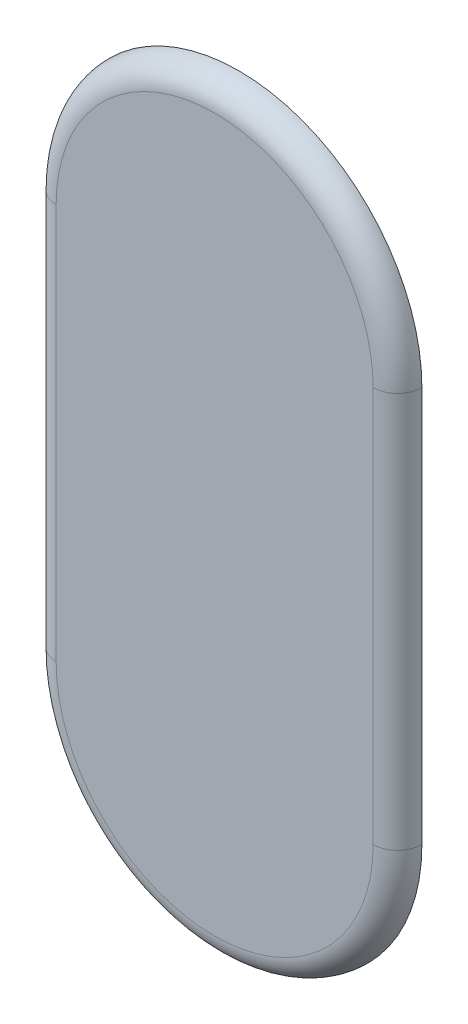
SolidWorks part; units mm, degrees
ref_plane "Plan de face" through (0, 0, 0) normal (0, 0, 1) x (1, 0, 0)
ref_plane "Plan de dessus" through (0, 0, 0) normal (0, 1, 0) x (1, 0, 0)
ref_plane "Plan de droite" through (0, 0, 0) normal (1, 0, 0) x (0, 0, -1)
sketch "Esquisse1" plane through (0, 0, 0) normal (0, 0, 1) x (1, 0, 0)
  line L1 (-75, 0) -> (75, 0)
  line L2 (-75, 0) -> (-75, -162.2766)
  line L3 (-75, -162.2766) -> (75, -162.2766)
  line L4 (75, 0) -> (75, -162.2766)
  circle A0 centre (0, 0) radius 75
  circle A1 centre (0, -162.2766) radius 75
extrude "Boss.-Extru.1" add sketch "Esquisse1" along normal blind 10 contours A1 L4 A0 L2 | L1 A0 | L1 A0 | L3 A1 | L3 A1 region at (0, 31.831, 0) region at (0, -81.1383, 0) region at (0, -31.831, 0) region at (0, -130.4456, 0) region at (0, -194.1076, 0)
fillet "Congé1" radius 10 4 edges at (0, 75, 10) (75, -81.1383, 10) (0, -237.2766, 10) (-75, -81.1383, 10)
